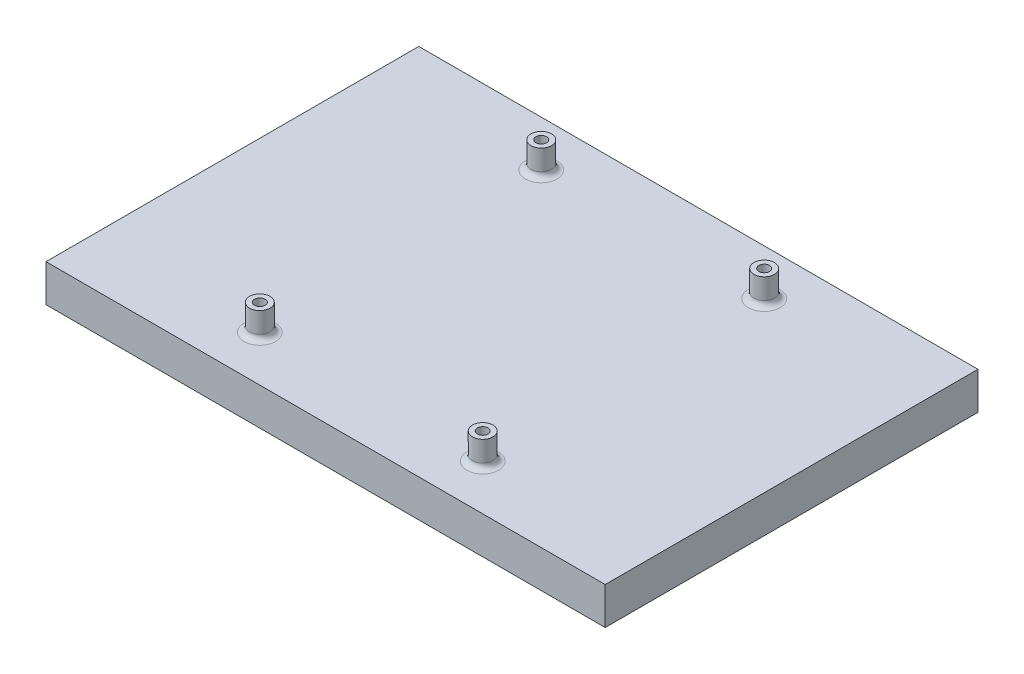
SolidWorks part; units mm, degrees
ref_plane "Front Plane" through (0, 0, 0) normal (0, 0, 1) x (1, 0, 0)
ref_plane "Top Plane" through (0, 0, 0) normal (0, 1, 0) x (1, 0, 0)
ref_plane "Right Plane" through (0, 0, 0) normal (1, 0, 0) x (0, 0, -1)
sketch "Sketch1" plane through (0, 0, 0) normal (0, 1, 0) x (1, 0, 0)
  line L1 (-75, 50) -> (75, 50)
  line L2 (-75, 50) -> (-75, -50)
  line L3 (-75, -50) -> (75, -50)
  line L4 (75, 50) -> (75, -50)
  line L5 (-75, 50) -> (75, -50) construction
  line L6 (-75, -50) -> (75, 50) construction
  point P0 (0, 0)
  dimension "D1" = 150
  dimension "D2" = 100
extrude "Boss-Extrude1" add sketch "Sketch1" along normal blind 10
sketch "Sketch2" plane through (0, 10, 0) normal (0, 1, 0) x (1, 0, 0)
  line L0 (75, -50) -> (75, 50) construction
  line L1 (0, 0) -> (0, 70.2566) construction
  line L2 (75, 50) -> (-75, 50) construction
  line L3 (0, 0) -> (146.4068, 0) construction
  circle A1 centre (29.9, 37.75) radius 2.75
  circle A2 centre (29.9, -37.75) radius 2.75
  circle A3 centre (-29.9, -37.75) radius 2.75
  circle A4 centre (-29.9, 37.75) radius 2.75
  point P0 (29.9, 37.75)
  point P8 (-29.9, -37.75)
  point P9 (29.9, -37.75)
  point P16 (-29.9, 37.75)
  dimension "D5" = 5.5
  dimension "D1" = 45.1
  dimension "D2" = 12.25
extrude "Boss-Extrude2" add sketch "Sketch2" along normal blind 7
hole_wizard "Ø1.0mm Dowel Hole1" positions "Sketch3" profile "Sketch4" hole size "Ø1.0" standard "ISO"
sketch "Sketch3" plane through (0, 17, 0) normal (0, 1, 0) x (1, 0, 0)
  point P0 (-29.9, 37.75)
  point P3 (29.9, 37.75)
  point P6 (29.9, -37.75)
  point P9 (-29.9, -37.75)
sketch "Sketch4" plane through (-29.9, 17, -37.75) normal (1, 0, 0) x (0, 0, 1)
  line L0 (0, 0) -> (0, 10.8562)
  line L1 (0, 10.8562) -> (1.425, 10)
  line L2 (1.425, 10) -> (1.425, 0)
  line L5 (1.425, 0) -> (0, 0)
  line L10 (0, 10.8562) -> (-1.425, 10) construction
  line L11 (0, -6.35) -> (0, 107.95) construction
  dimension "Hole Dia." = 2.85
  dimension "Hole Depth" = 10
  dimension "Drill Angle" = 118
fillet "Fillet1" radius 1.5 4 edges at (29.9, 10, 35) (-29.9, 10, 40.5) (29.9, 10, -35) (-29.9, 10, -40.5)
